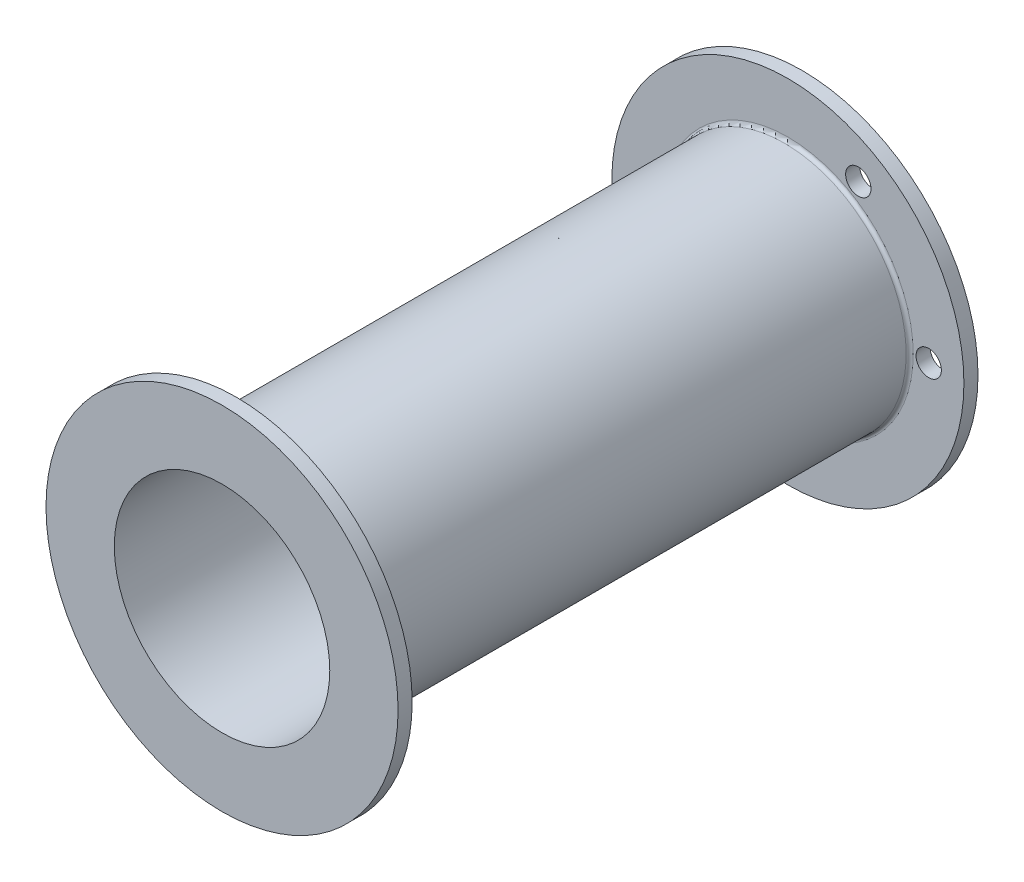
SolidWorks part; units mm, degrees
material "1060 Alloy"
ref_plane "Front Plane" through (0, 0, 0) normal (0, 0, 1) x (1, 0, 0)
ref_plane "Top Plane" through (0, 0, 0) normal (0, 1, 0) x (1, 0, 0)
ref_plane "Right Plane" through (0, 0, 0) normal (1, 0, 0) x (0, 0, -1)
sketch "Sketch1" plane through (0, 0, 0) normal (0, 0, 1) x (1, 0, 0)
  circle A0 centre (0, 0) radius 7.65
  circle A1 centre (0, 0) radius 8.65
  dimension "D1" = 15.3
  dimension "D2" = 17.3
extrude "Boss-Extrude1" add sketch "Sketch1" along normal blind 40.18
sketch "Sketch2" plane through (0, 0, 0) normal (0, 0, -1) x (-1, 0, 0)
  circle A0 centre (0, 0) radius 12.5
  circle A2 centre (0, 0) radius 7.65
  dimension "D1" = 25
extrude "Boss-Extrude2" add sketch "Sketch2" along normal blind 1
hole_wizard "M1.6 Clearance Hole1" positions "Sketch10" profile "Sketch11" hole size "M1.6" standard "ISO"
sketch "Sketch10" plane through (0, 0, 0) normal (0, 0, 1) x (1, 0, 0)
  point P0 (-10, 0)
  dimension "D1" = 10
sketch "Sketch11" plane through (-10, 0, 0) normal (1, 0, 0) x (0, -1, 0)
  line L0 (0, 0) -> (0, 5.5408)
  line L1 (0, 5.5408) -> (0.9, 5)
  line L2 (0.9, 5) -> (0.9, 0)
  line L5 (0.9, 0) -> (0, 0)
  line L10 (0, 5.5408) -> (-0.9, 5) construction
  line L11 (0, -6.35) -> (0, 107.95) construction
  dimension "Hole Dia." = 1.8
  dimension "Hole Depth" = 5
  dimension "Drill Angle" = 118
pattern_circular "CirPattern1" count 6 over 360 about axis through (0, 0, 0) along (0, 0, -1) skipping 1, 4 of "M1.6 Clearance Hole1"
fillet "Fillet1" radius 0.25 1 edges at (8.65, 0, 0)
ref_plane "Plane1" through (0, 0, 19.59) normal (0, 0, 1) x (1, 0, 0)
mirror "Mirror1" about plane through (0, 0, 19.59) normal (0, 0, 1) of "Boss-Extrude2"
